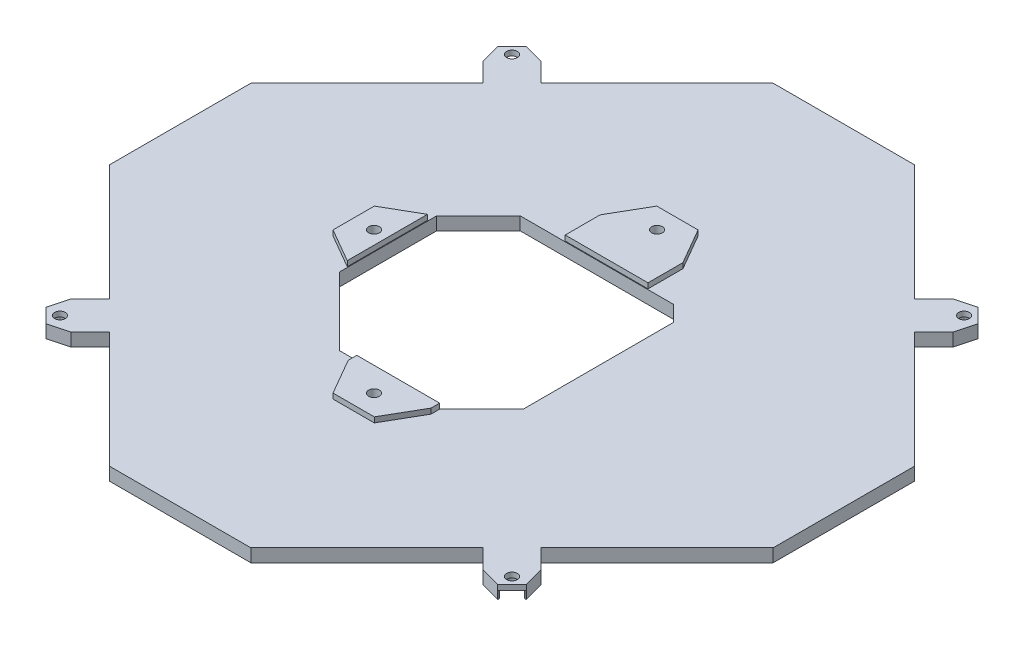
SolidWorks part; units mm, degrees
ref_plane "Front Plane" through (0, 0, 0) normal (0, 0, 1) x (1, 0, 0)
ref_plane "Top Plane" through (0, 0, 0) normal (0, 1, 0) x (1, 0, 0)
ref_plane "Right Plane" through (0, 0, 0) normal (1, 0, 0) x (0, 0, -1)
sketch "Sketch1" plane through (0, -273.8462, 0) normal (0, -1, 0) x (-1, 0, 0)
  line L0 (82.3028, 71.3418) -> (89.3773, 78.4163)
  line L1 (89.3773, 78.4163) -> (91.3931, 85.9396)
  line L2 (91.3931, 85.9396) -> (85.9404, 91.3923)
  line L3 (85.9404, 91.3923) -> (78.4171, 89.3765)
  line L4 (78.4171, 89.3765) -> (71.3427, 82.302)
  line L5 (82.3028, 71.3418) -> (82.02, 71.059)
  line L6 (71.3427, 82.302) -> (71.0598, 82.0192)
  line L7 (71.3418, -82.3028) -> (78.4163, -89.3773)
  line L8 (78.4163, -89.3773) -> (85.9396, -91.3931)
  line L9 (85.9396, -91.3931) -> (91.3923, -85.9404)
  line L10 (91.3923, -85.9404) -> (89.3765, -78.4171)
  line L11 (89.3765, -78.4171) -> (82.302, -71.3427)
  line L12 (71.3418, -82.3028) -> (71.059, -82.02)
  line L13 (82.302, -71.3427) -> (82.0192, -71.0598)
  line L14 (126.6447, 27) -> (126.6447, -27) construction
  line L15 (27.0002, -126.6453) -> (-26.9998, -126.6453) construction
  line L16 (-126.6447, -27) -> (-126.6447, 27) construction
  line L17 (-27, 126.6447) -> (27, 126.6447) construction
  line L18 (126.6447, 27) -> (126.6447, -27) construction
  line L19 (27.0002, -126.6453) -> (-26.9998, -126.6453) construction
  line L20 (-126.6447, -27) -> (-126.6447, 27) construction
  line L21 (-27, 126.6447) -> (27, 126.6447) construction
  line L22 (-126.6447, 27) -> (-27, 126.6447) construction
  line L23 (27, 126.6447) -> (126.6447, 27) construction
  line L24 (126.6447, -27) -> (27.0002, -126.6453) construction
  line L25 (-26.9998, -126.6453) -> (-126.6447, -27) construction
  line L26 (-26.8341, -126.2453) -> (-71.0599, -82.0193)
  line L27 (-126.2447, -26.8343) -> (-126.2447, 26.8343)
  line L28 (-28.1464, -5.25) -> (-33, -5.25)
  line L29 (-33, -5.25) -> (-33, -28.4962)
  line L30 (-33, -28.4962) -> (-17.0962, -44.4)
  line L31 (-17.0962, -44.4) -> (21.271, -44.4)
  line L32 (21.271, -44.4) -> (47.1748, -18.4962)
  line L33 (47.1748, -18.4962) -> (47.1748, 18.4962)
  line L34 (47.1748, 18.4962) -> (31.271, 34.4)
  line L35 (31.271, 34.4) -> (-27.0962, 34.4)
  line L36 (-27.0962, 34.4) -> (-33, 28.4962)
  line L37 (-33, 28.4962) -> (-33, 5.25)
  line L38 (-33, 5.25) -> (-28.1464, 5.25)
  line L39 (-28.1464, 5.25) -> (-21.5, 11.8964)
  line L40 (-21.5, 11.8964) -> (-21.5, -11.8964)
  line L41 (-21.5, -11.8964) -> (-28.1464, -5.25)
  line L42 (-28.1464, -5.25) -> (-33, -5.25) construction
  line L43 (-33, -5.25) -> (-33, -28.4962)
  line L44 (-33, -28.4962) -> (-17.0962, -44.4)
  line L45 (-17.0962, -44.4) -> (21.271, -44.4)
  line L46 (21.271, -44.4) -> (47.1748, -18.4962)
  line L47 (47.1748, -18.4962) -> (47.1748, 18.4962)
  line L48 (47.1748, 18.4962) -> (31.271, 34.4)
  line L49 (31.271, 34.4) -> (-27.0962, 34.4)
  line L50 (-27.0962, 34.4) -> (-33, 28.4962)
  line L51 (-33, 28.4962) -> (-33, 5.25)
  line L52 (-33, 5.25) -> (-28.1464, 5.25) construction
  line L53 (-28.1464, 5.25) -> (-21.5, 11.8964) construction
  line L54 (-21.5, 11.8964) -> (-21.5, -11.8964) construction
  line L55 (-21.5, -11.8964) -> (-28.1464, -5.25) construction
  line L56 (-126.2447, 26.8343) -> (-82.0192, 71.0598)
  line L57 (-26.8343, 126.2447) -> (26.8343, 126.2447)
  line L58 (26.8343, 126.2447) -> (71.0598, 82.0192)
  line L59 (126.2447, 26.8343) -> (126.2447, -26.8343)
  line L60 (126.2447, -26.8343) -> (82.0193, -71.06)
  line L61 (26.8345, -126.2453) -> (-26.8341, -126.2453)
  line L62 (-82.3028, -71.3418) -> (-89.3773, -78.4163)
  line L63 (-89.3773, -78.4163) -> (-91.3931, -85.9396)
  line L64 (-91.3931, -85.9396) -> (-85.9404, -91.3923)
  line L65 (-85.9404, -91.3923) -> (-78.4171, -89.3765)
  line L66 (-78.4171, -89.3765) -> (-71.3427, -82.302)
  line L67 (-71.3418, 82.3028) -> (-71.059, 82.02)
  line L68 (-82.302, 71.3427) -> (-82.0192, 71.0598)
  line L69 (-82.3028, -71.3418) -> (-82.02, -71.059)
  line L70 (-71.3427, -82.302) -> (-71.0598, -82.0192)
  line L71 (-82.0192, 71.0598) -> (-71.059, 82.02) construction
  line L72 (-71.3418, 82.3028) -> (-78.4163, 89.3773)
  line L73 (-78.4163, 89.3773) -> (-85.9396, 91.3931)
  line L74 (-85.9396, 91.3931) -> (-91.3923, 85.9404)
  line L75 (-89.3765, 78.4171) -> (-82.302, 71.3427)
  line L76 (-91.3923, 85.9404) -> (-89.3765, 78.4171)
  line L77 (-71.3418, 82.3028) -> (-78.4163, 89.3773)
  line L78 (-78.4163, 89.3773) -> (-85.9396, 91.3931)
  line L79 (-85.9396, 91.3931) -> (-91.3923, 85.9404)
  line L80 (-89.3765, 78.4171) -> (-82.302, 71.3427)
  line L81 (-91.3923, 85.9404) -> (-89.3765, 78.4171)
  line L82 (-71.059, 82.02) -> (-26.8343, 126.2447)
  line L83 (-126.2447, 26.8343) -> (-26.8343, 126.2447) construction
  line L84 (71.0598, 82.0192) -> (82.02, 71.059) construction
  line L85 (82.02, 71.059) -> (126.2447, 26.8343)
  line L86 (26.8343, 126.2447) -> (126.2447, 26.8343) construction
  line L87 (82.0193, -71.06) -> (71.0592, -82.0202) construction
  line L88 (71.0592, -82.0202) -> (26.8345, -126.2453)
  line L89 (126.2447, -26.8343) -> (26.8345, -126.2453) construction
  line L90 (-71.0599, -82.0193) -> (-82.0201, -71.0591) construction
  line L91 (-82.0201, -71.0591) -> (-126.2447, -26.8343)
  line L92 (-26.8341, -126.2453) -> (-126.2447, -26.8343) construction
  line L93 (-33, 5.25) -> (-33, -5.25)
  point P65 (0, 0)
  dimension "D1" = 0.25
  dimension "D2" = 0.4
  dimension "D3" = 0.25
  dimension "D4" = 4
extrude "Boss-Extrude1" add sketch "Sketch1" against normal offset from surface (4.95 mm away) 0.05 contours L91 L69 L62 L63 L64 L65 L66 L70 L26 L61 L88 L12 L7 L8 L9 L10 L11 L13 L60 L59 L85 L5 L0 L1 L2 L3 L4 L6 L58 L57 L82 L67 L77 L78 L79 L81 L80 L68 L56 L27 L93 L51 region at (-79.6365, -273.8462, -73.7253)
sketch "Sketch2" plane through (0, -268.8962, 0) normal (0, 1, 0) x (1, 0, 0)
  circle A0 centre (-86.0151, 86.0143) radius 2.05
  circle A1 centre (86.0143, 86.0151) radius 2.05
  circle A2 centre (86.0149, -86.0149) radius 2.05
  circle A3 centre (-86.0153, -86.0149) radius 2.05
  circle A5 centre (1.35, 53.8564) radius 2.05
  circle A6 centre (-52.5064, 0) radius 2.05
  circle A7 centre (1.35, -53.8564) radius 2.05
  dimension "D1" = 4.1
extrude "Cut-Extrude1" cut sketch "Sketch2" against normal through all
sketch "Sketch4" plane through (0, -268.8962, 0) normal (0, 1, 0) x (1, 0, 0)
  line L0 (17.35, 48) -> (17.35, 34.4) construction
  line L1 (27.0962, 34.4) -> (-31.271, 34.4) construction
  line L2 (17.35, 48) -> (17.35, 34.15) construction
  line L3 (-14.65, 48) -> (-14.65, 34.4) construction
  line L4 (-14.65, 34.15) -> (-14.65, 48) construction
  line L5 (-14.65, 34.4) -> (17.35, 34.4) construction
  line L6 (17.35, 48) -> (9.35, 61.8564) construction
  line L7 (9.35, 61.8564) -> (-6.65, 61.8564) construction
  line L8 (-6.65, 61.8564) -> (-14.65, 48) construction
  line L9 (-60.5064, 8) -> (-60.5064, -8) construction
  line L10 (-60.5064, -8) -> (-47.1748, -15.697) construction
  line L11 (-47.1748, 18.4962) -> (-47.1748, -18.4962) construction
  line L12 (-46.9248, -15.8413) -> (-60.5064, -8) construction
  line L13 (-60.5064, 8) -> (-47.1748, 15.697) construction
  line L14 (-60.5064, 8) -> (-46.9248, 15.8413) construction
  line L15 (-47.1748, 15.697) -> (-47.1748, -15.697) construction
  line L16 (-14.65, -44.4) -> (17.35, -44.4) construction
  line L17 (-21.271, -44.4) -> (17.0962, -44.4) construction
  line L18 (17.35, -44.4) -> (17.35, -48) construction
  line L19 (17.35, -48) -> (9.35, -61.8564) construction
  line L20 (-14.65, -48) -> (-14.65, -44.4) construction
  line L21 (9.35, -61.8564) -> (-6.65, -61.8564) construction
  line L22 (-6.65, -61.8564) -> (-14.65, -48) construction
  line L23 (17.1, 47.933) -> (17.1, 34.65)
  line L24 (-14.4, 34.65) -> (17.1, 34.65)
  line L25 (-14.4, 47.933) -> (-14.4, 34.65)
  line L26 (-6.5057, 61.6064) -> (-14.4, 47.933)
  line L27 (9.2057, 61.6064) -> (-6.5057, 61.6064)
  line L28 (17.1, 47.933) -> (9.2057, 61.6064)
  line L29 (-60.2564, 7.8557) -> (-60.2564, -7.8557)
  line L30 (-60.2564, -7.8557) -> (-47.4248, -15.264)
  line L31 (-47.4248, 15.264) -> (-47.4248, -15.264)
  line L32 (-60.2564, 7.8557) -> (-47.4248, 15.264)
  line L33 (-14.4, -44.65) -> (17.1, -44.65)
  line L34 (17.1, -44.65) -> (17.1, -47.933)
  line L35 (17.1, -47.933) -> (9.2057, -61.6064)
  line L36 (9.2057, -61.6064) -> (-6.5057, -61.6064)
  line L37 (-6.5057, -61.6064) -> (-14.4, -47.933)
  line L38 (-14.4, -47.933) -> (-14.4, -44.65)
  circle A0 centre (1.35, 53.8564) radius 2.05 construction
  circle A1 centre (-52.5064, 0) radius 2.05 construction
  circle A2 centre (1.35, -53.8564) radius 2.05 construction
  circle A3 centre (1.35, 53.8564) radius 2.05
  circle A4 centre (-52.5064, 0) radius 2.05
  circle A5 centre (1.35, -53.8564) radius 2.05
  dimension "D1" = 0.25
  dimension "D2" = 0.25
  dimension "D3" = 0.25
extrude "Boss-Extrude2" add sketch "Sketch4" along normal blind 2
sketch "Sketch5" plane through (0, -273.8462, 0) normal (0, -1, 0) x (1, 0, 0)
  line L0 (83.6285, 88.4014) -> (86.2799, 91.0529)
  line L1 (91.3931, 85.9396) -> (85.9404, 91.3923) construction
  line L2 (86.2799, 91.0529) -> (91.0529, 86.2799)
  line L3 (91.0529, 86.2799) -> (88.4014, 83.6285)
  line L4 (89.3773, 78.4163) -> (82.0201, 71.0591) construction
  line L5 (88.4014, -83.6285) -> (91.0529, -86.2799)
  line L6 (91.0529, -86.2799) -> (86.2799, -91.0529)
  line L7 (86.2799, -91.0529) -> (83.6285, -88.4014)
  line L8 (-83.6285, -88.4014) -> (-86.2799, -91.0529)
  line L9 (-86.2799, -91.0529) -> (-91.0529, -86.2799)
  line L10 (-91.0529, -86.2799) -> (-88.4014, -83.6285)
  line L11 (-88.4014, 83.6285) -> (-91.0529, 86.2799)
  line L12 (-91.0529, 86.2799) -> (-86.2799, 91.0529)
  line L13 (-86.2799, 91.0529) -> (-83.6285, 88.4014)
  arc A0 (83.6285, 88.4014) -> (88.4014, 83.6285) centre (86.0149, 86.0149) ccw
  circle A1 centre (1.35, 53.8564) radius 3.375
  circle A2 centre (-52.5064, 0) radius 3.375
  circle A3 centre (1.35, -53.8564) radius 3.375
  arc A6 (88.4014, 83.6285) -> (83.6285, 88.4014) centre (86.0149, 86.0149) ccw construction
  arc A7 (88.4014, -83.6285) -> (83.6285, -88.4014) centre (86.0149, -86.0149) ccw
  arc A8 (83.6285, -88.4014) -> (88.4014, -83.6285) centre (86.0149, -86.0149) ccw construction
  arc A9 (-83.6285, -88.4014) -> (-88.4014, -83.6285) centre (-86.0149, -86.0149) ccw
  arc A10 (-88.4014, -83.6285) -> (-83.6285, -88.4014) centre (-86.0149, -86.0149) ccw construction
  arc A11 (-88.4014, 83.6285) -> (-83.6285, 88.4014) centre (-86.0149, 86.0149) ccw
  arc A12 (-83.6285, 88.4014) -> (-88.4014, 83.6285) centre (-86.0149, 86.0149) ccw construction
  point P40 (0, 0)
  dimension "D1" = 6.75
  dimension "D2" = 4
extrude "Cut-Extrude2" cut sketch "Sketch5" against normal blind 3
fillet "Fillet1" radius 1 8 edges at (86.2799, -272.3462, -91.0529) (91.0529, -272.3462, -86.2799) (-86.2799, -272.3462, -91.0529) (-91.0529, -272.3462, -86.2799) (-91.0529, -272.3462, 86.2799) (-86.2799, -272.3462, 91.0529) (91.0529, -272.3462, 86.2799) (86.2799, -272.3462, 91.0529)
